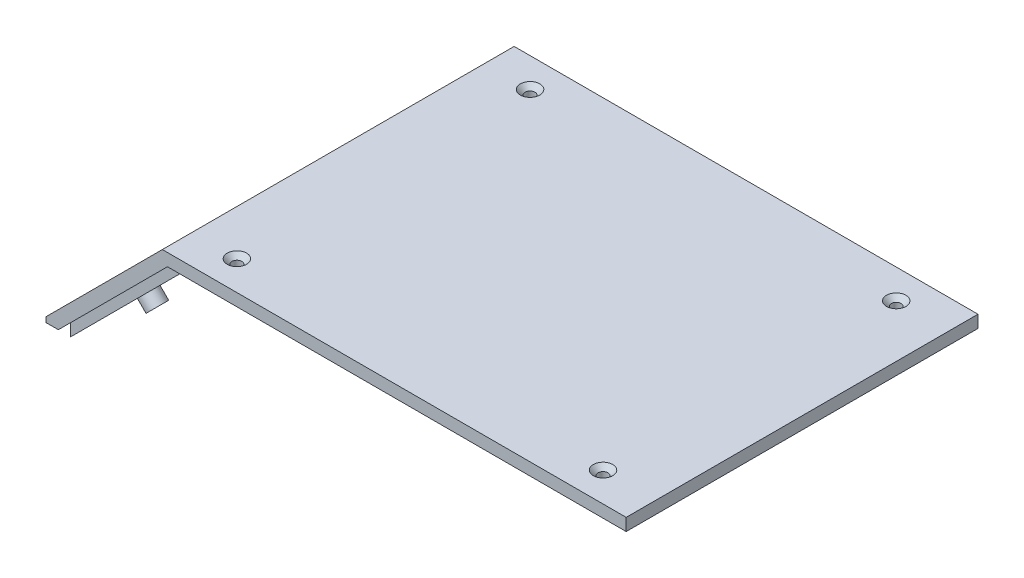
SolidWorks part; units mm, degrees
ref_plane "Front Plane" through (0, 0, 0) normal (0, 0, 1) x (1, 0, 0)
ref_plane "Top Plane" through (0, 0, 0) normal (0, 1, 0) x (1, 0, 0)
ref_plane "Right Plane" through (0, 0, 0) normal (1, 0, 0) x (0, 0, -1)
sketch "Sketch1" plane through (0, 0, 0) normal (0, 0, 1) x (1, 0, 0)
  line L0 (0, 0) -> (35.3553, 35.3553)
  line L1 (0, 0) -> (20.6791, 0) construction
  line L2 (35.3553, 35.3553) -> (184, 35.3553)
  line L3 (184, 35.3553) -> (184, 39.3553)
  line L4 (0, 0) -> (-4, 0)
  line L6 (33.6985, 39.3553) -> (184, 39.3553)
  line L7 (33.6985, 39.3553) -> (-4, 1.6569)
  line L8 (-4, 1.6569) -> (-4, 0)
  dimension "D1" = 50
  dimension "D2" = 45
  dimension "D3" = 184
  dimension "D4" = 4
  dimension "D5" = 4
  dimension "D6" = 4
extrude "Boss-Extrude1" add sketch "Sketch1" against normal blind 114 contours L6 L3 L2 L0 L4 L8 L7
sketch "Sketch3" plane through (0, 35.3553, 0) normal (0, -1, 0) x (1, 0, 0)
  line L0 (180, -4) -> (35.3553, -4)
  line L1 (35.3553, -114) -> (35.3553, 0) construction
  line L2 (35.3553, -4) -> (35.3553, -6)
  line L3 (35.3553, -6) -> (178, -6)
  line L4 (178, -6) -> (178, -108)
  line L5 (178, -108) -> (35.3553, -108)
  line L6 (35.3553, -108) -> (35.3553, -110)
  line L7 (35.3553, -110) -> (180, -110)
  line L8 (180, -110) -> (180, -4)
  line L9 (35.3553, 0) -> (184, 0) construction
  line L10 (184, -114) -> (184, 0) construction
  line L11 (35.3553, -114) -> (184, -114) construction
  dimension "D1" = 4
  dimension "D2" = 4
  dimension "D3" = 4
  dimension "D4" = 2
  dimension "D5" = 2
  dimension "D6" = 2
extrude "Boss-Extrude2" add sketch "Sketch3" along normal blind 4
sketch "Sketch5" plane through (0, 0, 0) normal (0.7071, -0.7071, 0) x (0, 0, -1)
  line L0 (4, 50) -> (4, 0)
  line L1 (114, 0) -> (0, 0) construction
  line L3 (6, 3) -> (6, 50)
  line L4 (108, 50) -> (108, 3)
  line L6 (110, 0) -> (110, 50)
  line L7 (4, 50) -> (6, 50)
  line L8 (108, 50) -> (110, 50)
  line L9 (4, 0) -> (110, 0)
  line L10 (6, 3) -> (108, 3)
  dimension "D1" = 3
extrude "Boss-Extrude3" add sketch "Sketch5" along direction (0, 1, 0) on the side of the normal blind 4 contours L10 L4 L8 L6 L9 L0 L7 L3
hole_wizard "CSK for M3 Flat Head Machine Screw2" positions "Sketch10" profile "Sketch11" countersink size "M3" standard "ANSI Metric" end condition up to next
sketch "Sketch10" plane through (0, 39.3553, 0) normal (0, 1, 0) x (1, 0, 0)
  point P0 (167, 9.5)
  point P3 (167, 104.5)
  point P6 (48.3553, 104.5)
  point P9 (48.3553, 9.5)
sketch "Sketch11" plane through (167, 39.3553, -9.5) normal (1, 0, 0) x (0, 0, 1)
  line L0 (0, 0) -> (0, 4)
  line L1 (0, 4) -> (1.6, 4)
  line L2 (1.6, 4) -> (1.6, 1.55)
  line L3 (1.6, 1.55) -> (3.15, 0)
  line L5 (3.15, 0) -> (0, 0)
  line L6 (-1.6, 1.55) -> (-3.15, 0) construction
  line L11 (0, -6.35) -> (0, 107.95) construction
  dimension "Thru Hole Dia." = 3.2
  dimension "Thru Hole Depth" = 4
  dimension "Near C'Sink Dia." = 6.3
  dimension "Near C'Sink Angle" = 90
sketch "Sketch12" plane through (0, 0, 0) normal (0.7071, -0.7071, 0) x (0, 0, -1)
  line L0 (57, 50) -> (57, 3) construction
  line L1 (108, 50) -> (6, 50) construction
  line L2 (6, 3) -> (108, 3) construction
  line L3 (6, 26.5) -> (108, 26.5) construction
  line L4 (24.75, 18.5) -> (89.25, 18.5)
  line L5 (24.75, 18.5) -> (24.75, 34.5)
  line L6 (24.75, 34.5) -> (89.25, 34.5)
  line L7 (89.25, 18.5) -> (89.25, 34.5)
  line L8 (24.75, 18.5) -> (89.25, 34.5) construction
  line L9 (24.75, 34.5) -> (89.25, 18.5) construction
  line L11 (6, 3) -> (6, 50) construction
  line L12 (108, 50) -> (108, 3) construction
  circle A1 centre (19.5, 42) radius 3
  circle A2 centre (19.5, 42) radius 1.25
  circle A3 centre (94.5, 42) radius 1.25
  circle A4 centre (94.5, 42) radius 3
  circle A5 centre (94.5, 11) radius 3
  circle A6 centre (94.5, 11) radius 1.25
  circle A7 centre (19.5, 11) radius 1.25
  circle A8 centre (19.5, 11) radius 3
  point P6 (57, 26.5)
  point P29 (18.4052, 41.0078)
  dimension "D3" = 2.5
  dimension "D4" = 6
  dimension "D1" = 64.5
  dimension "D2" = 16
  dimension "D5" = 75
  dimension "D6" = 31
extrude "Boss-Extrude4" add sketch "Sketch12" along normal blind 6.8 contours A1 A2 | A4 A3 | A5 A6 | A8 A7 region at (29.6985, 29.6985, -16.5849) region at (29.6985, 29.6985, -91.5849) region at (7.7782, 7.7782, -91.5849) region at (7.7782, 7.7782, -16.5849)
extrude "Cut-Extrude1" cut sketch "Sketch12<3>" against normal up to next contours L4 L7 L6 L5
sketch "Sketch12<3>" plane through (0, 0, 0) normal (0.7071, -0.7071, 0) x (0, 0, -1) same geometry as "Sketch12"
sketch "Sketch15" plane through (0, 35.3553, 0) normal (0, -1, 0) x (1, 0, 0)
  line L0 (180, -110) -> (180, -4) construction
  line L1 (110.5, -86) -> (141.5, -86) construction
  line L2 (110.5, -86) -> (110.5, -28) construction
  line L3 (110.5, -28) -> (141.5, -28) construction
  line L4 (141.5, -86) -> (141.5, -28) construction
  line L5 (110.5, -86) -> (141.5, -28) construction
  line L6 (110.5, -28) -> (141.5, -86) construction
  line L8 (35.3553, -57) -> (184, -57) construction
  line L9 (184, -114) -> (184, 0) construction
  line L10 (126, -86) -> (126, -28) construction
  circle A2 centre (110.5, -28) radius 1.25
  circle A3 centre (110.5, -28) radius 3
  circle A4 centre (110.5, -86) radius 3
  circle A5 centre (110.5, -86) radius 1.25
  circle A6 centre (141.5, -86) radius 1.25
  circle A7 centre (141.5, -86) radius 3
  circle A8 centre (141.5, -28) radius 3
  circle A9 centre (141.5, -28) radius 1.25
  circle A10 centre (80, -57) radius 1.25
  circle A11 centre (80, -57) radius 3
  point P0 (126, -57)
  dimension "D4" = 2.5
  dimension "D5" = 6
  dimension "D6" = 2.5
  dimension "D7" = 6
  dimension "D1" = 31
  dimension "D2" = 58
  dimension "D3" = 54
  dimension "D8" = 100
extrude "Boss-Extrude5" add sketch "Sketch15" along normal blind 6 contours A3 A2 | A8 A9 | A7 A6 | A4 A5 | A11 A10 region at (107.5849, 35.3553, -28) region at (107.5849, 35.3553, -86) region at (138.5849, 35.3553, -86) region at (138.5849, 35.3553, -28) region at (77.0849, 35.3553, -57)
